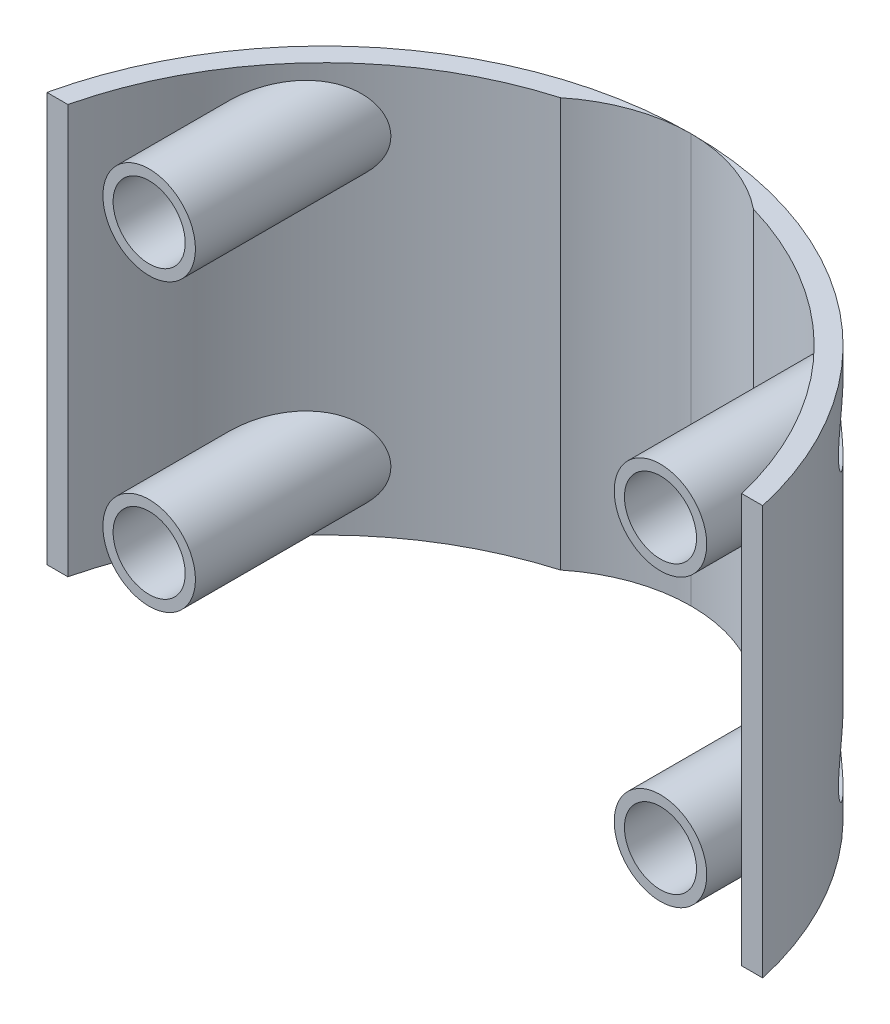
SolidWorks part; units mm, degrees
note: The reader was unsure of these and kept them because the rebuilt part matched: shared geometry of "Sketch2<4>", "Sketch2<5>", "Sketch2<6>".
ref_plane "Front Plane" through (0, 0, 0) normal (0, 0, 1) x (1, 0, 0)
ref_plane "Top Plane" through (0, 0, 0) normal (0, 1, 0) x (1, 0, 0)
ref_plane "Right Plane" through (0, 0, 0) normal (1, 0, 0) x (0, 0, -1)
sketch "Sketch1" plane through (0, 0, 0) normal (0, 1, 0) x (1, 0, 0)
  line L0 (-13, 0) -> (-13, -13)
  line L1 (13, 0) -> (13, -13)
  line L2 (15, 0) -> (15, -13)
  line L3 (-15, 0) -> (-15, -13)
  line L4 (-35, -13) -> (35, -13)
  line L5 (-9, 0) -> (-9, -13)
  line L6 (9, 0) -> (9, -13)
  circle A0 centre (0, 0) radius 13 construction
  circle A2 centre (0, 0) radius 15 construction
  arc A3 (13, 0) -> (-13, 0) centre (0, 0) ccw
  arc A4 (15, 0) -> (-15, 0) centre (0, 0) ccw
  arc A5 (-35, -13) -> (35, -13) centre (0, -20.875) cw
  arc A6 (-32.9469, -13) -> (32.9469, -13) centre (0, -20.875) cw
  circle A7 centre (0, 0) radius 9
  dimension "D1" = 26
  dimension "D2" = 2
  dimension "D7" = 18
  dimension "D3" = 13
  dimension "D5" = 20
  dimension "D6" = 20
  dimension "D4" = 2
extrude "Boss-Extrude1" add sketch "Sketch1" along normal blind 40 contours A4 A6 L4 A5 | L4 A6 A4 A5 | A7
sketch "Sketch2" plane through (0, 0, 13) normal (0, 0, 1) x (1, 0, 0)
  line L0 (0, 42.8817) -> (0, -5.917) construction
  circle A0 centre (25, 6) radius 3.525
  circle A1 centre (25, 6) radius 2
  circle A2 centre (25, 6) radius 4.525
  circle A3 centre (-25, 6) radius 2
  circle A4 centre (-25, 6) radius 3.525
  circle A5 centre (-25, 6) radius 4.525
  dimension "D1" = 4
  dimension "D2" = 1.525
  dimension "D3" = 1
  dimension "D4" = 25
  dimension "D5" = 6
extrude "Boss-Extrude2" add sketch "Sketch2" against normal up to next contours A2 A0 | A0 A1 | A5 A4 | A4 A3
extrude "Cut-Extrude1" cut sketch "Sketch2<4>" against normal blind 40 contours A1 | A3
sketch "Sketch2<4>" plane through (0, 0, 13) normal (0, 0, 1) x (1, 0, 0) same geometry as "Sketch2"
extrude "Cut-Extrude4" cut sketch "Sketch2<5>" along normal blind 9 from offset 22 contours A0 A1 | A4 A3 | A5 offset against normal yes
sketch "Sketch2<5>" plane through (0, 0, 13) normal (0, 0, 1) x (1, 0, 0) same geometry as "Sketch2"
pattern_linear "LPattern1" count 2 spacing 28 along (0, 1, 0) of "Boss-Extrude2", "Cut-Extrude1", "Cut-Extrude4"
extrude "Cut-Extrude5" cut sketch "Sketch2<6>" against normal blind 5 contours A4 A3 | A0 A1
sketch "Sketch2<6>" plane through (0, 0, 13) normal (0, 0, 1) x (1, 0, 0) same geometry as "Sketch2"
pattern_linear "LPattern2" count 2 spacing 28 along (0, 1, 0) of "Cut-Extrude5"
sketch "Sketch4" plane through (0, 0, 13) normal (0, 0, 1) x (1, 0, 0)
  circle A0 centre (-25, 6) radius 4.525 construction
  circle A1 centre (-25, 34) radius 4.525 construction
  circle A2 centre (25, 34) radius 3.525 construction
  circle A3 centre (25, 34) radius 2 construction
  circle A4 centre (25, 34) radius 4.525 construction
  circle A5 centre (25, 6) radius 4.525 construction
  circle A6 centre (25, 6) radius 3.525 construction
  circle A7 centre (25, 6) radius 2 construction
  circle A8 centre (-25, 6) radius 2 construction
  circle A9 centre (-25, 6) radius 3.525 construction
  circle A10 centre (-25, 34) radius 2 construction
  circle A11 centre (-25, 34) radius 3.525 construction
  circle A12 centre (-25, 6) radius 4.525
  circle A13 centre (-25, 34) radius 4.525
  circle A14 centre (25, 34) radius 3.525
  circle A15 centre (25, 34) radius 2
  circle A16 centre (25, 34) radius 4.525
  circle A17 centre (25, 6) radius 4.525
  circle A18 centre (25, 6) radius 3.525
  circle A19 centre (25, 6) radius 2
  circle A20 centre (-25, 6) radius 2
  circle A21 centre (-25, 6) radius 3.525
  circle A22 centre (-25, 34) radius 2
  circle A23 centre (-25, 34) radius 3.525
